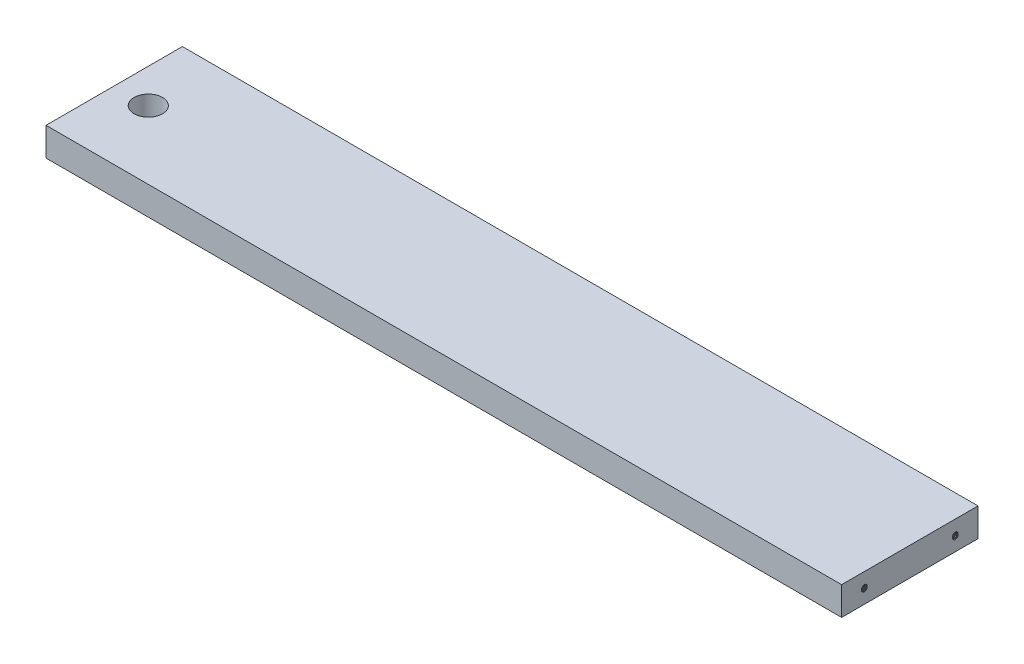
SolidWorks part; units mm, degrees
ref_plane "Front Plane" through (0, 0, 0) normal (0, 0, 1) x (1, 0, 0)
ref_plane "Top Plane" through (0, 0, 0) normal (0, 1, 0) x (1, 0, 0)
ref_plane "Right Plane" through (0, 0, 0) normal (1, 0, 0) x (0, 0, -1)
sketch "Sketch1" plane through (0, 0, 0) normal (0, 1, 0) x (1, 0, 0)
  line L1 (-350, 60) -> (350, 60)
  line L2 (-350, 60) -> (-350, -60)
  line L3 (-350, -60) -> (350, -60)
  line L4 (350, 60) -> (350, -60)
  line L5 (-350, 60) -> (350, -60) construction
  line L6 (-350, -60) -> (350, 60) construction
  point P0 (0, 0)
  dimension "D1" = 120
  dimension "D2" = 700
extrude "Boss-Extrude1" add sketch "Sketch1" along normal blind 25
sketch "Sketch2" plane through (0, 25, 0) normal (0, 1, 0) x (1, 0, 0)
  line L0 (-350, 60) -> (-350, -60) construction
  line L1 (-350, -60) -> (350, -60) construction
  circle A0 centre (-320, 0) radius 12.5
  dimension "D1" = 25
  dimension "D2" = 30
  dimension "D3" = 60
extrude "Cut-Extrude1" cut sketch "Sketch2" against normal through all
hole_wizard "#8 (0.199) Diameter Hole1" positions "Sketch21" profile "Sketch22" hole size "#8" standard "ANSI Inch"
sketch "Sketch21" plane through (350, 0, 0) normal (1, 0, 0) x (0, 0, -1)
  line L0 (-60, 0) -> (60, 0) construction
  line L1 (-60, 25) -> (-60, 0) construction
  point P0 (-40, 12.5)
  point P2 (40, 12.5)
  dimension "D1" = 80
  dimension "D2" = 12.5
  dimension "D3" = 20
sketch "Sketch22" plane through (350, 12.5, 40) normal (0, 1, 0) x (0, 0, -1)
  line L0 (0, 0) -> (0, 21.5186)
  line L1 (0, 21.5186) -> (2.5273, 20)
  line L2 (2.5273, 20) -> (2.5273, 0)
  line L5 (2.5273, 0) -> (0, 0)
  line L10 (0, 21.5186) -> (-2.5273, 20) construction
  line L11 (0, -6.35) -> (0, 107.95) construction
  dimension "Hole Dia." = 5.0546
  dimension "Hole Depth" = 20
  dimension "Drill Angle" = 118
sketch "Sketch30" plane through (350, 0, 0) normal (1, 0, 0) x (0, 0, -1)
  line L0 (-60, 25) -> (-60, 0) construction
  line L1 (-60, 25) -> (60, 25) construction
  circle A0 centre (-40, 12.5) radius 2.5273
  dimension "D3" = 5.0546
  dimension "D1" = 20
  dimension "D2" = 12.5
curve "Helix/Spiral1" pitch 1.25 height 22.8125 turns 18.25
ref_plane "Plane5" through (0, 12.5, 0) normal (0, -1, 0) x (-1, 0, 0)
sketch "Sketch31" plane through (0, 12.5, 0) normal (0, -1, 0) x (-1, 0, 0)
  line L0 (-327.5, -42.5273) -> (-326.875, -42.5273)
  line L1 (-326.875, -42.5273) -> (-327.1875, -43.0686)
  line L2 (-327.1875, -43.0686) -> (-327.5, -42.5273)
  spline S0 degree 3 poles (-350, -40) (-349.9741, -40.3287) (-349.9218, -40.9933) (-349.8438, -41.8333) (-349.7656, -42.3958) (-349.6875, -42.5931) (-349.6094, -42.3957) (-349.5313, -41.8336) (-349.4531, -40.9923) (-349.375, -40) (-349.2969, -39.0077) (-349.2188, -38.1664) (-349.1406, -37.6043) (-349.0625, -37.4069) (-348.9844, -37.6043) (-348.9063, -38.1664) (-348.8281, -39.0077) (-348.75, -40) (-348.6719, -40.9923) (-348.5938, -41.8336) (-348.5156, -42.3957) (-348.4375, -42.5931) (-348.3594, -42.3957) (-348.2813, -41.8336) (-348.2031, -40.9923) (-348.125, -40) (-348.0469, -39.0077) (-347.9688, -38.1664) (-347.8906, -37.6043) (-347.8125, -37.4069) (-347.7344, -37.6043) (-347.6563, -38.1664) (-347.5781, -39.0077) (-347.5, -40) (-347.4219, -40.9923) (-347.3438, -41.8336) (-347.2656, -42.3957) (-347.1875, -42.5931) (-347.1094, -42.3957) (-347.0312, -41.8336) (-346.9531, -40.9923) (-346.875, -40) (-346.7969, -39.0077) (-346.7187, -38.1664) (-346.6406, -37.6043) (-346.5625, -37.4069) (-346.4844, -37.6043) (-346.4062, -38.1664) (-346.3281, -39.0077) (-346.25, -40) (-346.1719, -40.9923) (-346.0938, -41.8336) (-346.0156, -42.3957) (-345.9375, -42.5931) (-345.8594, -42.3957) (-345.7812, -41.8336) (-345.7031, -40.9923) (-345.625, -40) (-345.5469, -39.0077) (-345.4688, -38.1664) (-345.3906, -37.6043) (-345.3125, -37.4069) (-345.2344, -37.6043) (-345.1563, -38.1664) (-345.0781, -39.0077) (-345, -40) (-344.9219, -40.9923) (-344.8438, -41.8336) (-344.7656, -42.3957) (-344.6875, -42.5931) (-344.6094, -42.3957) (-344.5312, -41.8336) (-344.4531, -40.9923) (-344.375, -40) (-344.2969, -39.0077) (-344.2188, -38.1664) (-344.1406, -37.6043) (-344.0625, -37.4069) (-343.9844, -37.6043) (-343.9062, -38.1664) (-343.8281, -39.0077) (-343.75, -40) (-343.6719, -40.9923) (-343.5938, -41.8336) (-343.5156, -42.3957) (-343.4375, -42.5931) (-343.3594, -42.3957) (-343.2813, -41.8336) (-343.2031, -40.9923) (-343.125, -40) (-343.0469, -39.0077) (-342.9687, -38.1664) (-342.8906, -37.6043) (-342.8125, -37.4069) (-342.7344, -37.6043) (-342.6563, -38.1664) (-342.5781, -39.0077) (-342.5, -40) (-342.4219, -40.9923) (-342.3437, -41.8336) (-342.2656, -42.3957) (-342.1875, -42.5931) (-342.1094, -42.3957) (-342.0312, -41.8336) (-341.9531, -40.9923) (-341.875, -40) (-341.7969, -39.0077) (-341.7188, -38.1664) (-341.6406, -37.6043) (-341.5625, -37.4069) (-341.4844, -37.6043) (-341.4063, -38.1664) (-341.3281, -39.0077) (-341.25, -40) (-341.1719, -40.9923) (-341.0938, -41.8336) (-341.0156, -42.3957) (-340.9375, -42.5931) (-340.8594, -42.3957) (-340.7812, -41.8336) (-340.7031, -40.9923) (-340.625, -40) (-340.5469, -39.0077) (-340.4688, -38.1664) (-340.3906, -37.6043) (-340.3125, -37.4069) (-340.2344, -37.6043) (-340.1562, -38.1664) (-340.0781, -39.0077) (-340, -40) (-339.9219, -40.9923) (-339.8438, -41.8336) (-339.7656, -42.3957) (-339.6875, -42.5931) (-339.6094, -42.3957) (-339.5312, -41.8336) (-339.4531, -40.9923) (-339.375, -40) (-339.2969, -39.0077) (-339.2188, -38.1664) (-339.1406, -37.6043) (-339.0625, -37.4069) (-338.9844, -37.6043) (-338.9062, -38.1664) (-338.8281, -39.0077) (-338.75, -40) (-338.6719, -40.9923) (-338.5938, -41.8336) (-338.5156, -42.3957) (-338.4375, -42.5931) (-338.3594, -42.3957) (-338.2812, -41.8336) (-338.2031, -40.9923) (-338.125, -40) (-338.0469, -39.0077) (-337.9688, -38.1664) (-337.8906, -37.6043) (-337.8125, -37.4069) (-337.7344, -37.6043) (-337.6563, -38.1664) (-337.5781, -39.0077) (-337.5, -40) (-337.4219, -40.9923) (-337.3437, -41.8336) (-337.2656, -42.3957) (-337.1875, -42.5931) (-337.1094, -42.3957) (-337.0312, -41.8336) (-336.9531, -40.9923) (-336.875, -40) (-336.7969, -39.0077) (-336.7188, -38.1664) (-336.6406, -37.6043) (-336.5625, -37.4069) (-336.4844, -37.6043) (-336.4063, -38.1664) (-336.3281, -39.0077) (-336.25, -40) (-336.1719, -40.9923) (-336.0938, -41.8336) (-336.0156, -42.3957) (-335.9375, -42.5931) (-335.8594, -42.3957) (-335.7812, -41.8336) (-335.7031, -40.9923) (-335.625, -40) (-335.5469, -39.0077) (-335.4688, -38.1664) (-335.3906, -37.6043) (-335.3125, -37.4069) (-335.2344, -37.6043) (-335.1562, -38.1664) (-335.0781, -39.0077) (-335, -40) (-334.9219, -40.9923) (-334.8438, -41.8336) (-334.7656, -42.3957) (-334.6875, -42.5931) (-334.6094, -42.3957) (-334.5312, -41.8336) (-334.4531, -40.9923) (-334.375, -40) (-334.2969, -39.0077) (-334.2188, -38.1664) (-334.1406, -37.6043) (-334.0625, -37.4069) (-333.9844, -37.6043) (-333.9062, -38.1664) (-333.8281, -39.0077) (-333.75, -40) (-333.6719, -40.9923) (-333.5938, -41.8336) (-333.5156, -42.3957) (-333.4375, -42.5931) (-333.3594, -42.3957) (-333.2813, -41.8336) (-333.2031, -40.9923) (-333.125, -40) (-333.0469, -39.0077) (-332.9687, -38.1664) (-332.8906, -37.6043) (-332.8125, -37.4069) (-332.7344, -37.6043) (-332.6563, -38.1664) (-332.5781, -39.0077) (-332.5, -40) (-332.4219, -40.9923) (-332.3438, -41.8336) (-332.2656, -42.3957) (-332.1875, -42.5931) (-332.1094, -42.3957) (-332.0312, -41.8336) (-331.9531, -40.9923) (-331.875, -40) (-331.7969, -39.0077) (-331.7188, -38.1664) (-331.6406, -37.6043) (-331.5625, -37.4069) (-331.4844, -37.6043) (-331.4063, -38.1664) (-331.3281, -39.0077) (-331.25, -40) (-331.1719, -40.9923) (-331.0938, -41.8336) (-331.0156, -42.3957) (-330.9375, -42.5931) (-330.8594, -42.3957) (-330.7813, -41.8336) (-330.7031, -40.9923) (-330.625, -40) (-330.5469, -39.0077) (-330.4688, -38.1664) (-330.3906, -37.6043) (-330.3125, -37.4069) (-330.2344, -37.6043) (-330.1563, -38.1664) (-330.0781, -39.0077) (-330, -40) (-329.9219, -40.9923) (-329.8438, -41.8336) (-329.7656, -42.3957) (-329.6875, -42.5931) (-329.6094, -42.3957) (-329.5313, -41.8336) (-329.4531, -40.9923) (-329.375, -40) (-329.2969, -39.0077) (-329.2187, -38.1664) (-329.1406, -37.6043) (-329.0625, -37.4069) (-328.9844, -37.6043) (-328.9063, -38.1664) (-328.8281, -39.0077) (-328.75, -40) (-328.6719, -40.9923) (-328.5937, -41.8336) (-328.5156, -42.3957) (-328.4375, -42.5931) (-328.3594, -42.3957) (-328.2812, -41.8336) (-328.2031, -40.9923) (-328.125, -40) (-328.0469, -39.0077) (-327.9687, -38.1664) (-327.8906, -37.6043) (-327.8125, -37.4069) (-327.7344, -37.6043) (-327.6562, -38.1664) (-327.5781, -39.0077) (-327.5, -40) (-327.4219, -40.9923) (-327.3437, -41.8336) (-327.2657, -42.3957) (-327.2134, -42.5273) (-327.1875, -42.5273) knots 0 0 0 0 0.003425 0.006849 0.010274 0.013699 0.017123 0.020548 0.023973 0.027397 0.030822 0.034247 0.037671 0.041096 0.044521 0.047945 0.05137 0.054795 0.058219 0.061644 0.065068 0.068493 0.071918 0.075342 0.078767 0.082192 0.085616 0.089041 0.092466 0.09589 0.099315 0.10274 0.106164 0.109589 0.113014 0.116438 0.119863 0.123288 0.126712 0.130137 0.133562 0.136986 0.140411 0.143836 0.14726 0.150685 0.15411 0.157534 0.160959 0.164384 0.167808 0.171233 0.174658 0.178082 0.181507 0.184932 0.188356 0.191781 0.195205 0.19863 0.202055 0.205479 0.208904 0.212329 0.215753 0.219178 0.222603 0.226027 0.229452 0.232877 0.236301 0.239726 0.243151 0.246575 0.25 0.253425 0.256849 0.260274 0.263699 0.267123 0.270548 0.273973 0.277397 0.280822 0.284247 0.287671 0.291096 0.294521 0.297945 0.30137 0.304795 0.308219 0.311644 0.315068 0.318493 0.321918 0.325342 0.328767 0.332192 0.335616 0.339041 0.342466 0.34589 0.349315 0.35274 0.356164 0.359589 0.363014 0.366438 0.369863 0.373288 0.376712 0.380137 0.383562 0.386986 0.390411 0.393836 0.39726 0.400685 0.40411 0.407534 0.410959 0.414384 0.417808 0.421233 0.424658 0.428082 0.431507 0.434932 0.438356 0.441781 0.445205 0.44863 0.452055 0.455479 0.458904 0.462329 0.465753 0.469178 0.472603 0.476027 0.479452 0.482877 0.486301 0.489726 0.493151 0.496575 0.5 0.503425 0.506849 0.510274 0.513699 0.517123 0.520548 0.523973 0.527397 0.530822 0.534247 0.537671 0.541096 0.544521 0.547945 0.55137 0.554795 0.558219 0.561644 0.565068 0.568493 0.571918 0.575342 0.578767 0.582192 0.585616 0.589041 0.592466 0.59589 0.599315 0.60274 0.606164 0.609589 0.613014 0.616438 0.619863 0.623288 0.626712 0.630137 0.633562 0.636986 0.640411 0.643836 0.64726 0.650685 0.65411 0.657534 0.660959 0.664384 0.667808 0.671233 0.674658 0.678082 0.681507 0.684932 0.688356 0.691781 0.695205 0.69863 0.702055 0.705479 0.708904 0.712329 0.715753 0.719178 0.722603 0.726027 0.729452 0.732877 0.736301 0.739726 0.743151 0.746575 0.75 0.753425 0.756849 0.760274 0.763699 0.767123 0.770548 0.773973 0.777397 0.780822 0.784247 0.787671 0.791096 0.794521 0.797945 0.80137 0.804795 0.808219 0.811644 0.815068 0.818493 0.821918 0.825342 0.828767 0.832192 0.835616 0.839041 0.842466 0.84589 0.849315 0.85274 0.856164 0.859589 0.863014 0.866438 0.869863 0.873288 0.876712 0.880137 0.883562 0.886986 0.890411 0.893836 0.89726 0.900685 0.90411 0.907534 0.910959 0.914384 0.917808 0.921233 0.924658 0.928082 0.931507 0.934932 0.938356 0.941781 0.945205 0.94863 0.952055 0.955479 0.958904 0.962329 0.965753 0.969178 0.972603 0.976027 0.979452 0.982877 0.986301 0.989726 0.993151 0.996575 1 1 1 1 construction
  point P6 (-327.1875, -42.5273)
  dimension "D1" = 0.625
sweep "Cut-Sweep1" cut profiles "Sketch31" path "Helix/Spiral1"
sketch "Sketch32" plane through (350, 0, 0) normal (1, 0, 0) x (0, 0, -1)
  circle A0 centre (40, 12.5) radius 2.5273
curve "Helix/Spiral2" pitch 1.25 height 20.3125 turns 16.25
sketch "Sketch33" plane through (0, 12.5, 0) normal (0, -1, 0) x (-1, 0, 0)
  line L0 (-330.0521, 37.4732) -> (-329.3304, 37.4732)
  line L1 (-329.3304, 37.4732) -> (-329.6912, 36.8482)
  line L2 (-329.6912, 36.8482) -> (-330.0521, 37.4732)
  spline S0 degree 3 poles (-350, 40) (-349.9741, 39.6713) (-349.9218, 39.0067) (-349.8438, 38.1667) (-349.7656, 37.6042) (-349.6875, 37.4069) (-349.6094, 37.6043) (-349.5313, 38.1664) (-349.4531, 39.0077) (-349.375, 40) (-349.2969, 40.9923) (-349.2188, 41.8336) (-349.1406, 42.3957) (-349.0625, 42.5931) (-348.9844, 42.3957) (-348.9063, 41.8336) (-348.8281, 40.9923) (-348.75, 40) (-348.6719, 39.0077) (-348.5938, 38.1664) (-348.5156, 37.6043) (-348.4375, 37.4069) (-348.3594, 37.6043) (-348.2812, 38.1664) (-348.2031, 39.0077) (-348.125, 40) (-348.0469, 40.9923) (-347.9687, 41.8336) (-347.8906, 42.3957) (-347.8125, 42.5931) (-347.7344, 42.3957) (-347.6563, 41.8336) (-347.5781, 40.9923) (-347.5, 40) (-347.4219, 39.0077) (-347.3437, 38.1664) (-347.2656, 37.6043) (-347.1875, 37.4069) (-347.1094, 37.6043) (-347.0312, 38.1664) (-346.9531, 39.0077) (-346.875, 40) (-346.7969, 40.9923) (-346.7188, 41.8336) (-346.6406, 42.3957) (-346.5625, 42.5931) (-346.4844, 42.3957) (-346.4062, 41.8336) (-346.3281, 40.9923) (-346.25, 40) (-346.1719, 39.0077) (-346.0937, 38.1664) (-346.0156, 37.6043) (-345.9375, 37.4069) (-345.8594, 37.6043) (-345.7812, 38.1664) (-345.7031, 39.0077) (-345.625, 40) (-345.5469, 40.9923) (-345.4687, 41.8336) (-345.3906, 42.3957) (-345.3125, 42.5931) (-345.2344, 42.3957) (-345.1563, 41.8336) (-345.0781, 40.9923) (-345, 40) (-344.9219, 39.0077) (-344.8437, 38.1664) (-344.7656, 37.6043) (-344.6875, 37.4069) (-344.6094, 37.6043) (-344.5312, 38.1664) (-344.4531, 39.0077) (-344.375, 40) (-344.2969, 40.9923) (-344.2187, 41.8336) (-344.1406, 42.3957) (-344.0625, 42.5931) (-343.9844, 42.3957) (-343.9062, 41.8336) (-343.8281, 40.9923) (-343.75, 40) (-343.6719, 39.0077) (-343.5938, 38.1664) (-343.5156, 37.6043) (-343.4375, 37.4069) (-343.3594, 37.6043) (-343.2813, 38.1664) (-343.2031, 39.0077) (-343.125, 40) (-343.0469, 40.9923) (-342.9688, 41.8336) (-342.8906, 42.3957) (-342.8125, 42.5931) (-342.7344, 42.3957) (-342.6563, 41.8336) (-342.5781, 40.9923) (-342.5, 40) (-342.4219, 39.0077) (-342.3438, 38.1664) (-342.2656, 37.6043) (-342.1875, 37.4069) (-342.1094, 37.6043) (-342.0312, 38.1664) (-341.9531, 39.0077) (-341.875, 40) (-341.7969, 40.9923) (-341.7188, 41.8336) (-341.6406, 42.3957) (-341.5625, 42.5931) (-341.4844, 42.3957) (-341.4062, 41.8336) (-341.3281, 40.9923) (-341.25, 40) (-341.1719, 39.0077) (-341.0938, 38.1664) (-341.0156, 37.6043) (-340.9375, 37.4069) (-340.8594, 37.6043) (-340.7813, 38.1664) (-340.7031, 39.0077) (-340.625, 40) (-340.5469, 40.9923) (-340.4688, 41.8336) (-340.3906, 42.3957) (-340.3125, 42.5931) (-340.2344, 42.3957) (-340.1563, 41.8336) (-340.0781, 40.9923) (-340, 40) (-339.9219, 39.0077) (-339.8437, 38.1664) (-339.7656, 37.6043) (-339.6875, 37.4069) (-339.6094, 37.6043) (-339.5312, 38.1664) (-339.4531, 39.0077) (-339.375, 40) (-339.2969, 40.9923) (-339.2187, 41.8336) (-339.1406, 42.3957) (-339.0625, 42.5931) (-338.9844, 42.3957) (-338.9062, 41.8336) (-338.8281, 40.9923) (-338.75, 40) (-338.6719, 39.0077) (-338.5937, 38.1664) (-338.5156, 37.6043) (-338.4375, 37.4069) (-338.3594, 37.6043) (-338.2812, 38.1664) (-338.2031, 39.0077) (-338.125, 40) (-338.0469, 40.9923) (-337.9687, 41.8336) (-337.8906, 42.3957) (-337.8125, 42.5931) (-337.7344, 42.3957) (-337.6562, 41.8336) (-337.5781, 40.9923) (-337.5, 40) (-337.4219, 39.0077) (-337.3437, 38.1664) (-337.2656, 37.6043) (-337.1875, 37.4069) (-337.1094, 37.6043) (-337.0312, 38.1664) (-336.9531, 39.0077) (-336.875, 40) (-336.7969, 40.9923) (-336.7187, 41.8336) (-336.6406, 42.3957) (-336.5625, 42.5931) (-336.4844, 42.3957) (-336.4062, 41.8336) (-336.3281, 40.9923) (-336.25, 40) (-336.1719, 39.0077) (-336.0938, 38.1664) (-336.0156, 37.6043) (-335.9375, 37.4069) (-335.8594, 37.6043) (-335.7813, 38.1664) (-335.7031, 39.0077) (-335.625, 40) (-335.5469, 40.9923) (-335.4688, 41.8336) (-335.3906, 42.3957) (-335.3125, 42.5931) (-335.2344, 42.3957) (-335.1562, 41.8336) (-335.0781, 40.9923) (-335, 40) (-334.9219, 39.0077) (-334.8437, 38.1664) (-334.7656, 37.6043) (-334.6875, 37.4069) (-334.6094, 37.6043) (-334.5312, 38.1664) (-334.4531, 39.0077) (-334.375, 40) (-334.2969, 40.9923) (-334.2187, 41.8336) (-334.1406, 42.3957) (-334.0625, 42.5931) (-333.9844, 42.3957) (-333.9062, 41.8336) (-333.8281, 40.9923) (-333.75, 40) (-333.6719, 39.0077) (-333.5937, 38.1664) (-333.5156, 37.6043) (-333.4375, 37.4069) (-333.3594, 37.6043) (-333.2812, 38.1664) (-333.2031, 39.0077) (-333.125, 40) (-333.0469, 40.9923) (-332.9687, 41.8336) (-332.8906, 42.3957) (-332.8125, 42.5931) (-332.7344, 42.3957) (-332.6562, 41.8336) (-332.5781, 40.9923) (-332.5, 40) (-332.4219, 39.0077) (-332.3437, 38.1664) (-332.2656, 37.6043) (-332.1875, 37.4069) (-332.1094, 37.6043) (-332.0312, 38.1664) (-331.9531, 39.0077) (-331.875, 40) (-331.7969, 40.9923) (-331.7188, 41.8336) (-331.6406, 42.3957) (-331.5625, 42.5931) (-331.4844, 42.3957) (-331.4062, 41.8336) (-331.3281, 40.9923) (-331.25, 40) (-331.1719, 39.0077) (-331.0938, 38.1664) (-331.0156, 37.6043) (-330.9375, 37.4069) (-330.8594, 37.6043) (-330.7812, 38.1664) (-330.7031, 39.0077) (-330.625, 40) (-330.5469, 40.9923) (-330.4687, 41.8336) (-330.3906, 42.3957) (-330.3125, 42.5931) (-330.2344, 42.3957) (-330.1562, 41.8336) (-330.0781, 40.9923) (-330, 40) (-329.9219, 39.0077) (-329.8437, 38.1664) (-329.7657, 37.6043) (-329.7134, 37.4727) (-329.6875, 37.4727) knots 0 0 0 0 0.003846 0.007692 0.011538 0.015385 0.019231 0.023077 0.026923 0.030769 0.034615 0.038462 0.042308 0.046154 0.05 0.053846 0.057692 0.061538 0.065385 0.069231 0.073077 0.076923 0.080769 0.084615 0.088462 0.092308 0.096154 0.1 0.103846 0.107692 0.111538 0.115385 0.119231 0.123077 0.126923 0.130769 0.134615 0.138462 0.142308 0.146154 0.15 0.153846 0.157692 0.161538 0.165385 0.169231 0.173077 0.176923 0.180769 0.184615 0.188462 0.192308 0.196154 0.2 0.203846 0.207692 0.211538 0.215385 0.219231 0.223077 0.226923 0.230769 0.234615 0.238462 0.242308 0.246154 0.25 0.253846 0.257692 0.261538 0.265385 0.269231 0.273077 0.276923 0.280769 0.284615 0.288462 0.292308 0.296154 0.3 0.303846 0.307692 0.311538 0.315385 0.319231 0.323077 0.326923 0.330769 0.334615 0.338462 0.342308 0.346154 0.35 0.353846 0.357692 0.361538 0.365385 0.369231 0.373077 0.376923 0.380769 0.384615 0.388462 0.392308 0.396154 0.4 0.403846 0.407692 0.411538 0.415385 0.419231 0.423077 0.426923 0.430769 0.434615 0.438462 0.442308 0.446154 0.45 0.453846 0.457692 0.461538 0.465385 0.469231 0.473077 0.476923 0.480769 0.484615 0.488462 0.492308 0.496154 0.5 0.503846 0.507692 0.511538 0.515385 0.519231 0.523077 0.526923 0.530769 0.534615 0.538462 0.542308 0.546154 0.55 0.553846 0.557692 0.561538 0.565385 0.569231 0.573077 0.576923 0.580769 0.584615 0.588462 0.592308 0.596154 0.6 0.603846 0.607692 0.611538 0.615385 0.619231 0.623077 0.626923 0.630769 0.634615 0.638462 0.642308 0.646154 0.65 0.653846 0.657692 0.661538 0.665385 0.669231 0.673077 0.676923 0.680769 0.684615 0.688462 0.692308 0.696154 0.7 0.703846 0.707692 0.711538 0.715385 0.719231 0.723077 0.726923 0.730769 0.734615 0.738462 0.742308 0.746154 0.75 0.753846 0.757692 0.761538 0.765385 0.769231 0.773077 0.776923 0.780769 0.784615 0.788462 0.792308 0.796154 0.8 0.803846 0.807692 0.811538 0.815385 0.819231 0.823077 0.826923 0.830769 0.834615 0.838462 0.842308 0.846154 0.85 0.853846 0.857692 0.861538 0.865385 0.869231 0.873077 0.876923 0.880769 0.884615 0.888462 0.892308 0.896154 0.9 0.903846 0.907692 0.911538 0.915385 0.919231 0.923077 0.926923 0.930769 0.934615 0.938462 0.942308 0.946154 0.95 0.953846 0.957692 0.961538 0.965385 0.969231 0.973077 0.976923 0.980769 0.984615 0.988462 0.992308 0.996154 1 1 1 1 construction
  point P2 (-329.6912, 37.4732)
  dimension "D1" = 0.625
sweep "Cut-Sweep2" cut profiles "Sketch33" path "Helix/Spiral2"
